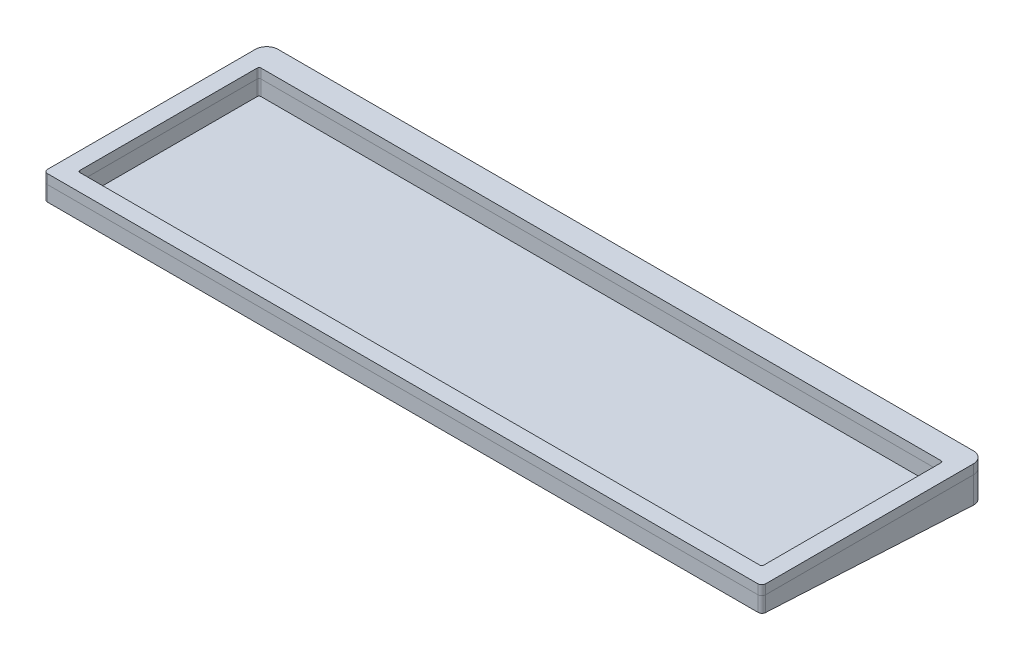
SolidWorks part; units mm, degrees
ref_plane "Front Plane" through (0, 0, 0) normal (0, 0, 1) x (1, 0, 0)
ref_plane "Top Plane" through (0, 0, 0) normal (0, 1, 0) x (1, 0, 0)
ref_plane "Right Plane" through (0, 0, 0) normal (1, 0, 0) x (0, 0, -1)
sketch "Sketch1" plane through (0, 0, 0) normal (0, 1, 0) x (1, 0, 0)
  line L1 (-178.825, 47.625) -> (178.825, 47.625)
  line L2 (-179.825, 46.625) -> (-179.825, -46.625)
  line L3 (-178.825, -47.625) -> (178.825, -47.625)
  line L4 (179.825, 46.625) -> (179.825, -46.625)
  line L5 (-179.825, 47.625) -> (179.825, -47.625) construction
  line L6 (-179.825, -47.625) -> (179.825, 47.625) construction
  arc A0 (178.825, -47.625) -> (179.825, -46.625) centre (178.825, -46.625) ccw
  arc A1 (178.825, 47.625) -> (179.825, 46.625) centre (178.825, 46.625) cw
  arc A2 (-179.825, -46.625) -> (-178.825, -47.625) centre (-178.825, -46.625) ccw
  arc A3 (-178.825, 47.625) -> (-179.825, 46.625) centre (-178.825, 46.625) ccw
  circle A4 centre (157.075, 19.175) radius 1.1
  circle A5 centre (136.925, -16.775) radius 1.1
  circle A6 centre (-153.475, 33.725) radius 1.1
  circle A7 centre (17.925, 22.275) radius 1.1
  circle A8 centre (17.875, -35.075) radius 1.1
  circle A9 centre (-130.375, -35.725) radius 1.1
  point P0 (0, 0)
  dimension "D3" = 1
  dimension "D4" = 2.2
  dimension "D7" = 2.2
  dimension "D8" = 2.2
  dimension "D9" = 2.2
  dimension "D10" = 2.2
  dimension "D11" = 2.2
  dimension "D1" = 359.65
  dimension "D2" = 95.25
  dimension "D5" = 22.75
  dimension "D6" = 28.45
  dimension "D12" = 42.9
  dimension "D13" = 30.85
  dimension "D14" = 25.35
  dimension "D15" = 161.9
  dimension "D16" = 12.55
  dimension "D17" = 161.95
  dimension "D18" = 11.9
  dimension "D19" = 49.45
  dimension "D20" = 13.9
  dimension "D21" = 26.35
sketch "Sketch2" plane through (0, 0, 0) normal (0, 1, 0) x (1, 0, 0)
  line L0 (-179.825, 46.625) -> (-179.825, -46.625) construction
  line L1 (-178.825, -47.625) -> (178.825, -47.625) construction
  line L2 (179.825, 46.625) -> (179.825, -46.625) construction
  line L3 (-178.825, 47.625) -> (178.825, 47.625) construction
  line L4 (-179.825, 46.625) -> (-179.825, -46.625)
  line L5 (-178.825, -47.625) -> (178.825, -47.625)
  line L6 (179.825, 46.625) -> (179.825, -46.625)
  line L7 (-178.825, 47.625) -> (178.825, 47.625)
  line L9 (-182.825, 60.625) -> (182.825, 60.625)
  line L10 (-188.825, 54.625) -> (-188.825, -54.625)
  line L11 (-186.825, -56.625) -> (186.825, -56.625)
  line L12 (188.825, 54.625) -> (188.825, -54.625)
  circle A0 centre (157.075, 19.175) radius 1.1 construction
  circle A1 centre (136.925, -16.775) radius 1.1 construction
  circle A2 centre (17.875, -35.075) radius 1.1 construction
  circle A3 centre (17.925, 22.275) radius 1.1 construction
  circle A4 centre (-153.475, 33.725) radius 1.1 construction
  circle A5 centre (-130.375, -35.725) radius 1.1 construction
  arc A6 (-179.825, -46.625) -> (-178.825, -47.625) centre (-178.825, -46.625) ccw construction
  arc A7 (178.825, -47.625) -> (179.825, -46.625) centre (178.825, -46.625) ccw construction
  arc A8 (179.825, 46.625) -> (178.825, 47.625) centre (178.825, 46.625) ccw construction
  arc A9 (-178.825, 47.625) -> (-179.825, 46.625) centre (-178.825, 46.625) ccw construction
  circle A10 centre (157.075, 19.175) radius 1.1
  circle A11 centre (136.925, -16.775) radius 1.1
  circle A12 centre (17.875, -35.075) radius 1.1
  circle A13 centre (17.925, 22.275) radius 1.1
  circle A14 centre (-153.475, 33.725) radius 1.1
  circle A15 centre (-130.375, -35.725) radius 1.1
  arc A16 (-179.825, -46.625) -> (-178.825, -47.625) centre (-178.825, -46.625) ccw
  arc A17 (178.825, -47.625) -> (179.825, -46.625) centre (178.825, -46.625) ccw
  arc A18 (179.825, 46.625) -> (178.825, 47.625) centre (178.825, 46.625) ccw
  arc A19 (-178.825, 47.625) -> (-179.825, 46.625) centre (-178.825, 46.625) ccw
  arc A20 (182.825, 60.625) -> (188.825, 54.625) centre (182.825, 54.625) cw
  arc A21 (-182.825, 60.625) -> (-188.825, 54.625) centre (-182.825, 54.625) ccw
  arc A22 (186.825, -56.625) -> (188.825, -54.625) centre (186.825, -54.625) ccw
  arc A23 (-188.825, -54.625) -> (-186.825, -56.625) centre (-186.825, -54.625) ccw
  point P30 (0, 0)
  dimension "D5" = 6
  dimension "D6" = 2
  dimension "D1" = 13
  dimension "D2" = 9
  dimension "D3" = 9
  dimension "D4" = 9
extrude "Boss-Extrude1" add sketch "Sketch2" along normal blind 13 contours L10 A23 L11 A22 L12 A20 L9 A21 A19 L7 A18 L6 A17 L5 A16 L4 region at (0, 0, -56.6707)
sketch "Sketch4" plane through (0, 0, 0) normal (0, -1, 0) x (1, 0, 0)
  line L0 (188.825, -54.625) -> (188.825, 54.625) construction
  line L1 (-182.825, -60.625) -> (182.825, -60.625) construction
  line L2 (-188.825, -54.625) -> (-188.825, 54.625) construction
  line L3 (-186.825, 56.625) -> (186.825, 56.625) construction
  line L4 (-179.825, 46.625) -> (-179.825, -46.625)
  line L5 (178.825, 47.625) -> (-178.825, 47.625)
  line L6 (179.825, -46.625) -> (179.825, 46.625)
  line L7 (-178.825, -47.625) -> (178.825, -47.625)
  line L8 (-179.825, 46.625) -> (-179.825, -46.625)
  line L10 (179.825, -46.625) -> (179.825, 46.625)
  line L11 (-178.825, -47.625) -> (178.825, -47.625)
  line L12 (188.825, -54.625) -> (188.825, 54.625)
  line L13 (-182.825, -60.625) -> (182.825, -60.625)
  line L14 (-188.825, -54.625) -> (-188.825, 54.625)
  line L15 (-186.825, 56.625) -> (186.825, 56.625)
  arc A0 (188.825, 54.625) -> (186.825, 56.625) centre (186.825, 54.625) ccw construction
  arc A1 (182.825, -60.625) -> (188.825, -54.625) centre (182.825, -54.625) ccw construction
  arc A2 (-188.825, -54.625) -> (-182.825, -60.625) centre (-182.825, -54.625) ccw construction
  arc A3 (-186.825, 56.625) -> (-188.825, 54.625) centre (-186.825, 54.625) ccw construction
  arc A4 (-179.825, -46.625) -> (-178.825, -47.625) centre (-178.825, -46.625) ccw
  arc A5 (-178.825, 47.625) -> (-179.825, 46.625) centre (-178.825, 46.625) ccw
  arc A6 (179.825, 46.625) -> (178.825, 47.625) centre (178.825, 46.625) ccw
  arc A7 (178.825, -47.625) -> (179.825, -46.625) centre (178.825, -46.625) ccw
  arc A8 (-179.825, -46.625) -> (-178.825, -47.625) centre (-178.825, -46.625) ccw
  arc A9 (-178.825, 47.625) -> (-179.825, 46.625) centre (-178.825, 46.625) ccw
  arc A10 (179.825, 46.625) -> (178.825, 47.625) centre (178.825, 46.625) ccw
  arc A11 (178.825, -47.625) -> (179.825, -46.625) centre (178.825, -46.625) ccw
  arc A12 (188.825, 54.625) -> (186.825, 56.625) centre (186.825, 54.625) ccw
  arc A13 (182.825, -60.625) -> (188.825, -54.625) centre (182.825, -54.625) ccw
  arc A14 (-188.825, -54.625) -> (-182.825, -60.625) centre (-182.825, -54.625) ccw
  arc A15 (-186.825, 56.625) -> (-188.825, 54.625) centre (-186.825, 54.625) ccw
  arc M9 (-178.825, -47.625) -> (-179.825, -46.625) centre (-178.825, -46.625) cw
  line M10 (-179.825, -46.625) -> (-179.825, 46.625)
  arc M11 (-179.825, 46.625) -> (-178.825, 47.625) centre (-178.825, 46.625) cw
  line M12 (-178.825, 47.625) -> (178.825, 47.625)
  arc M13 (178.825, 47.625) -> (179.825, 46.625) centre (178.825, 46.625) cw
  line M14 (179.825, 46.625) -> (179.825, -46.625)
  arc M15 (179.825, -46.625) -> (178.825, -47.625) centre (178.825, -46.625) cw
  line M16 (178.825, -47.625) -> (-178.825, -47.625)
  line M17 (-188.825, 54.625) -> (-188.825, -54.625)
  arc M18 (-188.825, -54.625) -> (-182.825, -60.625) centre (-182.825, -54.625) ccw
  line M19 (-182.825, -60.625) -> (182.825, -60.625)
  arc M20 (182.825, -60.625) -> (188.825, -54.625) centre (182.825, -54.625) ccw
  line M21 (188.825, -54.625) -> (188.825, 54.625)
  arc M22 (188.825, 54.625) -> (186.825, 56.625) centre (186.825, 54.625) ccw
  line M23 (186.825, 56.625) -> (-186.825, 56.625)
  arc M24 (-186.825, 56.625) -> (-188.825, 54.625) centre (-186.825, 54.625) ccw
  dimension "D1" = 0
extrude "Boss-Extrude3" add sketch "Sketch4" along normal blind 10.5 contours M24 M17 M18 M19 M20 M21 M22 M23 M16 M9 M10 M11 M12 M13 M14 M15 | M9 M16 M15 M14 M13 M12 M11 M10 region at (0, 0, 0) region at (184.2715, 0, -56.0715)
sketch "Sketch8" plane through (-188.825, 0, 0) normal (-1, 0, 0) x (0, 0, 1)
  line L0 (54.625, 0) -> (-57.625, 0) construction
  line L2 (-60.625, 13) -> (-60.625, -10.5) construction
  line L4 (-60.625, -6.1448) -> (-60.625, -10.5)
  line L5 (-60.625, -10.5) -> (56.625, -10.5)
  line L11 (56.625, 0) -> (56.625, -10.5)
  line L12 (56.625, 13) -> (56.625, -10.5) construction
  line L13 (-60.625, -6.1448) -> (56.625, 0)
  dimension "D1" = 2
  dimension "D2" = 10.5
  dimension "D3" = 87
extrude "Cut-Extrude4" cut sketch "Sketch8" against normal blind 400
sketch "Sketch9" plane through (0, 0, 0) normal (0, 1, 0) x (1, 0, 0)
  line L0 (-121.9453, 45.1) -> (-108.9453, 45.1)
  line L1 (-121.9453, 31.1) -> (-108.9453, 31.1)
  line L2 (-122.4453, 44.6) -> (-122.4453, 31.6)
  line L3 (-108.4453, 44.6) -> (-108.4453, 31.6)
  line L4 (-102.8953, 45.1) -> (-89.8953, 45.1)
  line L5 (-102.8953, 31.1) -> (-89.8953, 31.1)
  line L6 (-103.3953, 44.6) -> (-103.3953, 31.6)
  line L7 (-89.3953, 44.6) -> (-89.3953, 31.6)
  line L8 (-83.8453, 45.1) -> (-70.8453, 45.1)
  line L9 (-83.8453, 31.1) -> (-70.8453, 31.1)
  line L10 (-84.3453, 44.6) -> (-84.3453, 31.6)
  line L11 (-70.3453, 44.6) -> (-70.3453, 31.6)
  line L12 (-64.7953, 45.1) -> (-51.7953, 45.1)
  line L13 (-64.7953, 31.1) -> (-51.7953, 31.1)
  line L14 (-65.2953, 44.6) -> (-65.2953, 31.6)
  line L15 (-51.2953, 44.6) -> (-51.2953, 31.6)
  line L16 (-45.7453, 45.1) -> (-32.7453, 45.1)
  line L17 (-45.7453, 31.1) -> (-32.7453, 31.1)
  line L18 (-46.2453, 44.6) -> (-46.2453, 31.6)
  line L19 (-32.2453, 44.6) -> (-32.2453, 31.6)
  line L20 (-26.6953, 45.1) -> (-13.6953, 45.1)
  line L21 (-26.6953, 31.1) -> (-13.6953, 31.1)
  line L22 (-27.1953, 44.6) -> (-27.1953, 31.6)
  line L23 (-13.1953, 44.6) -> (-13.1953, 31.6)
  line L24 (-7.6453, 45.1) -> (5.3547, 45.1)
  line L25 (-7.6453, 31.1) -> (5.3547, 31.1)
  line L26 (-8.1453, 44.6) -> (-8.1453, 31.6)
  line L27 (5.8547, 44.6) -> (5.8547, 31.6)
  line L28 (11.4047, 45.1) -> (24.4047, 45.1)
  line L29 (11.4047, 31.1) -> (24.4047, 31.1)
  line L30 (10.9047, 44.6) -> (10.9047, 31.6)
  line L31 (24.9047, 44.6) -> (24.9047, 31.6)
  line L32 (30.4547, 45.1) -> (43.4547, 45.1)
  line L33 (30.4547, 31.1) -> (43.4547, 31.1)
  line L34 (29.9547, 44.6) -> (29.9547, 31.6)
  line L35 (43.9547, 44.6) -> (43.9547, 31.6)
  line L36 (49.5047, 45.1) -> (62.5047, 45.1)
  line L37 (49.5047, 31.1) -> (62.5047, 31.1)
  line L38 (49.0047, 44.6) -> (49.0047, 31.6)
  line L39 (63.0047, 44.6) -> (63.0047, 31.6)
  line L40 (68.5547, 45.1) -> (81.5547, 45.1)
  line L41 (68.5547, 31.1) -> (81.5547, 31.1)
  line L42 (68.0547, 44.6) -> (68.0547, 31.6)
  line L43 (82.0547, 44.6) -> (82.0547, 31.6)
  line L44 (87.6047, 45.1) -> (100.6047, 45.1)
  line L45 (87.6047, 31.1) -> (100.6047, 31.1)
  line L46 (87.1047, 44.6) -> (87.1047, 31.6)
  line L47 (101.1047, 44.6) -> (101.1047, 31.6)
  line L48 (106.6547, 45.1) -> (119.6547, 45.1)
  line L49 (106.6547, 31.1) -> (119.6547, 31.1)
  line L50 (106.1547, 44.6) -> (106.1547, 31.6)
  line L51 (120.1547, 44.6) -> (120.1547, 31.6)
  line L52 (135.2297, 45.1) -> (148.2297, 45.1)
  line L53 (135.2297, 31.1) -> (148.2297, 31.1)
  line L54 (134.7297, 44.6) -> (134.7297, 31.6)
  line L55 (148.7297, 44.6) -> (148.7297, 31.6)
  line L56 (150.6677, 44.1) -> (156.6677, 44.1)
  line L57 (150.6677, 29.1) -> (156.6677, 29.1)
  line L58 (150.1677, 43.6) -> (150.1677, 29.6)
  line L59 (157.1677, 43.6) -> (157.1677, 29.6)
  line L60 (126.7917, 44.1) -> (132.7917, 44.1)
  line L61 (126.7917, 29.1) -> (132.7917, 29.1)
  line L62 (126.2917, 43.6) -> (126.2917, 29.6)
  line L63 (133.2917, 43.6) -> (133.2917, 29.6)
  line L64 (163.8047, 45.1) -> (176.8047, 45.1)
  line L65 (163.8047, 31.1) -> (176.8047, 31.1)
  line L66 (163.3047, 44.6) -> (163.3047, 31.6)
  line L67 (177.3047, 44.6) -> (177.3047, 31.6)
  line L68 (-117.1828, 26.05) -> (-104.1828, 26.05)
  line L69 (-117.1828, 12.05) -> (-104.1828, 12.05)
  line L70 (-117.6828, 25.55) -> (-117.6828, 12.55)
  line L71 (-103.6828, 25.55) -> (-103.6828, 12.55)
  line L72 (-93.3703, 26.05) -> (-80.3703, 26.05)
  line L73 (-93.3703, 12.05) -> (-80.3703, 12.05)
  line L74 (-93.8703, 25.55) -> (-93.8703, 12.55)
  line L75 (-79.8703, 25.55) -> (-79.8703, 12.55)
  line L76 (-74.3203, 26.05) -> (-61.3203, 26.05)
  line L77 (-74.3203, 12.05) -> (-61.3203, 12.05)
  line L78 (-74.8203, 25.55) -> (-74.8203, 12.55)
  line L79 (-60.8203, 25.55) -> (-60.8203, 12.55)
  line L80 (-55.2703, 26.05) -> (-42.2703, 26.05)
  line L81 (-55.2703, 12.05) -> (-42.2703, 12.05)
  line L82 (-55.7703, 25.55) -> (-55.7703, 12.55)
  line L83 (-41.7703, 25.55) -> (-41.7703, 12.55)
  line L84 (-36.2203, 26.05) -> (-23.2203, 26.05)
  line L85 (-36.2203, 12.05) -> (-23.2203, 12.05)
  line L86 (-36.7203, 25.55) -> (-36.7203, 12.55)
  line L87 (-22.7203, 25.55) -> (-22.7203, 12.55)
  line L88 (-17.1703, 26.05) -> (-4.1703, 26.05)
  line L89 (-17.1703, 12.05) -> (-4.1703, 12.05)
  line L90 (-17.6703, 25.55) -> (-17.6703, 12.55)
  line L91 (-3.6703, 25.55) -> (-3.6703, 12.55)
  line L92 (1.8797, 26.05) -> (14.8797, 26.05)
  line L93 (1.8797, 12.05) -> (14.8797, 12.05)
  line L94 (1.3797, 25.55) -> (1.3797, 12.55)
  line L95 (15.3797, 25.55) -> (15.3797, 12.55)
  line L96 (20.9297, 26.05) -> (33.9297, 26.05)
  line L97 (20.9297, 12.05) -> (33.9297, 12.05)
  line L98 (20.4297, 25.55) -> (20.4297, 12.55)
  line L99 (34.4297, 25.55) -> (34.4297, 12.55)
  line L100 (39.9797, 26.05) -> (52.9797, 26.05)
  line L101 (39.9797, 12.05) -> (52.9797, 12.05)
  line L102 (39.4797, 25.55) -> (39.4797, 12.55)
  line L103 (53.4797, 25.55) -> (53.4797, 12.55)
  line L104 (59.0297, 26.05) -> (72.0297, 26.05)
  line L105 (59.0297, 12.05) -> (72.0297, 12.05)
  line L106 (58.5297, 25.55) -> (58.5297, 12.55)
  line L107 (72.5297, 25.55) -> (72.5297, 12.55)
  line L108 (78.0797, 26.05) -> (91.0797, 26.05)
  line L109 (78.0797, 12.05) -> (91.0797, 12.05)
  line L110 (77.5797, 25.55) -> (77.5797, 12.55)
  line L111 (91.5797, 25.55) -> (91.5797, 12.55)
  line L112 (97.1297, 26.05) -> (110.1297, 26.05)
  line L113 (97.1297, 12.05) -> (110.1297, 12.05)
  line L114 (96.6297, 25.55) -> (96.6297, 12.55)
  line L115 (110.6297, 25.55) -> (110.6297, 12.55)
  line L116 (116.1797, 26.05) -> (129.1797, 26.05)
  line L117 (116.1797, 12.05) -> (129.1797, 12.05)
  line L118 (115.6797, 25.55) -> (115.6797, 12.55)
  line L119 (129.6797, 25.55) -> (129.6797, 12.55)
  line L120 (139.9922, 26.05) -> (152.9922, 26.05)
  line L121 (139.9922, 12.05) -> (152.9922, 12.05)
  line L122 (139.4922, 25.55) -> (139.4922, 12.55)
  line L123 (153.4922, 25.55) -> (153.4922, 12.55)
  line L124 (163.8047, 26.05) -> (176.8047, 26.05)
  line L125 (163.8047, 12.05) -> (176.8047, 12.05)
  line L126 (163.3047, 25.55) -> (163.3047, 12.55)
  line L127 (177.3047, 25.55) -> (177.3047, 12.55)
  line L128 (-114.8016, 7) -> (-101.8016, 7)
  line L129 (-114.8016, -7) -> (-101.8016, -7)
  line L130 (-115.3016, 6.5) -> (-115.3016, -6.5)
  line L131 (-101.3016, 6.5) -> (-101.3016, -6.5)
  line L132 (-88.6078, 7) -> (-75.6078, 7)
  line L133 (-88.6078, -7) -> (-75.6078, -7)
  line L134 (-89.1078, 6.5) -> (-89.1078, -6.5)
  line L135 (-75.1078, 6.5) -> (-75.1078, -6.5)
  line L136 (-69.5578, 7) -> (-56.5578, 7)
  line L137 (-69.5578, -7) -> (-56.5578, -7)
  line L138 (-70.0578, 6.5) -> (-70.0578, -6.5)
  line L139 (-56.0578, 6.5) -> (-56.0578, -6.5)
  line L140 (-50.5078, 7) -> (-37.5078, 7)
  line L141 (-50.5078, -7) -> (-37.5078, -7)
  line L142 (-51.0078, 6.5) -> (-51.0078, -6.5)
  line L143 (-37.0078, 6.5) -> (-37.0078, -6.5)
  line L144 (-31.4578, 7) -> (-18.4578, 7)
  line L145 (-31.4578, -7) -> (-18.4578, -7)
  line L146 (-31.9578, 6.5) -> (-31.9578, -6.5)
  line L147 (-17.9578, 6.5) -> (-17.9578, -6.5)
  line L148 (-12.4078, 7) -> (0.5922, 7)
  line L149 (-12.4078, -7) -> (0.5922, -7)
  line L150 (-12.9078, 6.5) -> (-12.9078, -6.5)
  line L151 (1.0922, 6.5) -> (1.0922, -6.5)
  line L152 (6.6422, 7) -> (19.6422, 7)
  line L153 (6.6422, -7) -> (19.6422, -7)
  line L154 (6.1422, 6.5) -> (6.1422, -6.5)
  line L155 (20.1422, 6.5) -> (20.1422, -6.5)
  line L156 (25.6922, 7) -> (38.6922, 7)
  line L157 (25.6922, -7) -> (38.6922, -7)
  line L158 (25.1922, 6.5) -> (25.1922, -6.5)
  line L159 (39.1922, 6.5) -> (39.1922, -6.5)
  line L160 (44.7422, 7) -> (57.7422, 7)
  line L161 (44.7422, -7) -> (57.7422, -7)
  line L162 (44.2422, 6.5) -> (44.2422, -6.5)
  line L163 (58.2422, 6.5) -> (58.2422, -6.5)
  line L164 (63.7922, 7) -> (76.7922, 7)
  line L165 (63.7922, -7) -> (76.7922, -7)
  line L166 (63.2922, 6.5) -> (63.2922, -6.5)
  line L167 (77.2922, 6.5) -> (77.2922, -6.5)
  line L168 (82.8422, 7) -> (95.8422, 7)
  line L169 (82.8422, -7) -> (95.8422, -7)
  line L170 (82.3422, 6.5) -> (82.3422, -6.5)
  line L171 (96.3422, 6.5) -> (96.3422, -6.5)
  line L172 (101.8922, 7) -> (114.8922, 7)
  line L173 (101.8922, -7) -> (114.8922, -7)
  line L174 (101.3922, 6.5) -> (101.3922, -6.5)
  line L175 (115.3922, 6.5) -> (115.3922, -6.5)
  line L176 (132.8484, 7) -> (145.8484, 7)
  line L177 (132.8484, -7) -> (145.8484, -7)
  line L178 (132.3484, 6.5) -> (132.3484, -6.5)
  line L179 (146.3484, 6.5) -> (146.3484, -6.5)
  line L180 (148.2864, 6) -> (154.2864, 6)
  line L181 (148.2864, -9) -> (154.2864, -9)
  line L182 (147.7864, 5.5) -> (147.7864, -8.5)
  line L183 (154.7864, 5.5) -> (154.7864, -8.5)
  line L184 (124.4104, 6) -> (130.4104, 6)
  line L185 (124.4104, -9) -> (130.4104, -9)
  line L186 (123.9104, 5.5) -> (123.9104, -8.5)
  line L187 (130.9104, 5.5) -> (130.9104, -8.5)
  line L188 (163.8047, 7) -> (176.8047, 7)
  line L189 (163.8047, -7) -> (176.8047, -7)
  line L190 (163.3047, 6.5) -> (163.3047, -6.5)
  line L191 (177.3047, 6.5) -> (177.3047, -6.5)
  line L192 (-110.0391, -12.05) -> (-97.0391, -12.05)
  line L193 (-110.0391, -26.05) -> (-97.0391, -26.05)
  line L194 (-110.5391, -12.55) -> (-110.5391, -25.55)
  line L195 (-96.5391, -12.55) -> (-96.5391, -25.55)
  line L196 (-94.6011, -13.05) -> (-88.6011, -13.05)
  line L197 (-94.6011, -28.05) -> (-88.6011, -28.05)
  line L198 (-95.1011, -13.55) -> (-95.1011, -27.55)
  line L199 (-88.1011, -13.55) -> (-88.1011, -27.55)
  line L200 (-118.4771, -13.05) -> (-112.4771, -13.05)
  line L201 (-118.4771, -28.05) -> (-112.4771, -28.05)
  line L202 (-118.9771, -13.55) -> (-118.9771, -27.55)
  line L203 (-111.9771, -13.55) -> (-111.9771, -27.55)
  line L204 (-79.0828, -12.05) -> (-66.0828, -12.05)
  line L205 (-79.0828, -26.05) -> (-66.0828, -26.05)
  line L206 (-79.5828, -12.55) -> (-79.5828, -25.55)
  line L207 (-65.5828, -12.55) -> (-65.5828, -25.55)
  line L208 (-60.0328, -12.05) -> (-47.0328, -12.05)
  line L209 (-60.0328, -26.05) -> (-47.0328, -26.05)
  line L210 (-60.5328, -12.55) -> (-60.5328, -25.55)
  line L211 (-46.5328, -12.55) -> (-46.5328, -25.55)
  line L212 (-40.9828, -12.05) -> (-27.9828, -12.05)
  line L213 (-40.9828, -26.05) -> (-27.9828, -26.05)
  line L214 (-41.4828, -12.55) -> (-41.4828, -25.55)
  line L215 (-27.4828, -12.55) -> (-27.4828, -25.55)
  line L216 (-21.9328, -12.05) -> (-8.9328, -12.05)
  line L217 (-21.9328, -26.05) -> (-8.9328, -26.05)
  line L218 (-22.4328, -12.55) -> (-22.4328, -25.55)
  line L219 (-8.4328, -12.55) -> (-8.4328, -25.55)
  line L220 (-2.8828, -12.05) -> (10.1172, -12.05)
  line L221 (-2.8828, -26.05) -> (10.1172, -26.05)
  line L222 (-3.3828, -12.55) -> (-3.3828, -25.55)
  line L223 (10.6172, -12.55) -> (10.6172, -25.55)
  line L224 (16.1672, -12.05) -> (29.1672, -12.05)
  line L225 (16.1672, -26.05) -> (29.1672, -26.05)
  line L226 (15.6672, -12.55) -> (15.6672, -25.55)
  line L227 (29.6672, -12.55) -> (29.6672, -25.55)
  line L228 (35.2172, -12.05) -> (48.2172, -12.05)
  line L229 (35.2172, -26.05) -> (48.2172, -26.05)
  line L230 (34.7172, -12.55) -> (34.7172, -25.55)
  line L231 (48.7172, -12.55) -> (48.7172, -25.55)
  line L232 (54.2672, -12.05) -> (67.2672, -12.05)
  line L233 (54.2672, -26.05) -> (67.2672, -26.05)
  line L234 (53.7672, -12.55) -> (53.7672, -25.55)
  line L235 (67.7672, -12.55) -> (67.7672, -25.55)
  line L236 (73.3172, -12.05) -> (86.3172, -12.05)
  line L237 (73.3172, -26.05) -> (86.3172, -26.05)
  line L238 (72.8172, -12.55) -> (72.8172, -25.55)
  line L239 (86.8172, -12.55) -> (86.8172, -25.55)
  line L240 (92.3672, -12.05) -> (105.3672, -12.05)
  line L241 (92.3672, -26.05) -> (105.3672, -26.05)
  line L242 (91.8672, -12.55) -> (91.8672, -25.55)
  line L243 (105.8672, -12.55) -> (105.8672, -25.55)
  line L244 (118.5609, -12.05) -> (131.5609, -12.05)
  line L245 (118.5609, -26.05) -> (131.5609, -26.05)
  line L246 (118.0609, -12.55) -> (118.0609, -25.55)
  line L247 (132.0609, -12.55) -> (132.0609, -25.55)
  line L248 (144.7547, -12.05) -> (157.7547, -12.05)
  line L249 (144.7547, -26.05) -> (157.7547, -26.05)
  line L250 (144.2547, -12.55) -> (144.2547, -25.55)
  line L251 (158.2547, -12.55) -> (158.2547, -25.55)
  line L252 (163.8047, -12.05) -> (176.8047, -12.05)
  line L253 (163.8047, -26.05) -> (176.8047, -26.05)
  line L254 (163.3047, -12.55) -> (163.3047, -25.55)
  line L255 (177.3047, -12.55) -> (177.3047, -25.55)
  line L256 (-119.5641, -31.1) -> (-106.5641, -31.1)
  line L257 (-119.5641, -45.1) -> (-106.5641, -45.1)
  line L258 (-120.0641, -31.6) -> (-120.0641, -44.6)
  line L259 (-106.0641, -31.6) -> (-106.0641, -44.6)
  line L260 (-95.7516, -31.1) -> (-82.7516, -31.1)
  line L261 (-95.7516, -45.1) -> (-82.7516, -45.1)
  line L262 (-96.2516, -31.6) -> (-96.2516, -44.6)
  line L263 (-82.2516, -31.6) -> (-82.2516, -44.6)
  line L264 (-71.9391, -31.1) -> (-58.9391, -31.1)
  line L265 (-71.9391, -45.1) -> (-58.9391, -45.1)
  line L266 (-72.4391, -31.6) -> (-72.4391, -44.6)
  line L267 (-58.4391, -31.6) -> (-58.4391, -44.6)
  line L268 (-0.5016, -31.1) -> (12.4984, -31.1)
  line L269 (-0.5016, -45.1) -> (12.4984, -45.1)
  line L270 (-1.0016, -31.6) -> (-1.0016, -44.6)
  line L271 (12.9984, -31.6) -> (12.9984, -44.6)
  line L272 (52.9984, -32.1) -> (58.9984, -32.1)
  line L273 (52.9984, -47.1) -> (58.9984, -47.1)
  line L274 (52.4984, -32.6) -> (52.4984, -46.6)
  line L275 (59.4984, -32.6) -> (59.4984, -46.6)
  line L276 (-47.0016, -32.1) -> (-41.0016, -32.1)
  line L277 (-47.0016, -47.1) -> (-41.0016, -47.1)
  line L278 (-47.5016, -32.6) -> (-47.5016, -46.6)
  line L279 (-40.5016, -32.6) -> (-40.5016, -46.6)
  line L280 (68.5547, -31.1) -> (81.5547, -31.1)
  line L281 (68.5547, -45.1) -> (81.5547, -45.1)
  line L282 (68.0547, -31.6) -> (68.0547, -44.6)
  line L283 (82.0547, -31.6) -> (82.0547, -44.6)
  line L284 (87.6047, -31.1) -> (100.6047, -31.1)
  line L285 (87.6047, -45.1) -> (100.6047, -45.1)
  line L286 (87.1047, -31.6) -> (87.1047, -44.6)
  line L287 (101.1047, -31.6) -> (101.1047, -44.6)
  line L288 (106.6547, -31.1) -> (119.6547, -31.1)
  line L289 (106.6547, -45.1) -> (119.6547, -45.1)
  line L290 (106.1547, -31.6) -> (106.1547, -44.6)
  line L291 (120.1547, -31.6) -> (120.1547, -44.6)
  line L292 (125.7047, -31.1) -> (138.7047, -31.1)
  line L293 (125.7047, -45.1) -> (138.7047, -45.1)
  line L294 (125.2047, -31.6) -> (125.2047, -44.6)
  line L295 (139.2047, -31.6) -> (139.2047, -44.6)
  line L296 (144.7547, -31.1) -> (157.7547, -31.1)
  line L297 (144.7547, -45.1) -> (157.7547, -45.1)
  line L298 (144.2547, -31.6) -> (144.2547, -44.6)
  line L299 (158.2547, -31.6) -> (158.2547, -44.6)
  line L300 (163.8047, -31.1) -> (176.8047, -31.1)
  line L301 (163.8047, -45.1) -> (176.8047, -45.1)
  line L302 (163.3047, -31.6) -> (163.3047, -44.6)
  line L303 (177.3047, -31.6) -> (177.3047, -44.6)
  line L304 (-124.9703, 47.625) -> (-103.2456, 47.625)
  line L305 (-124.9703, -47.625) -> (179.8297, -47.625)
  line L306 (-124.9703, 47.625) -> (-124.9703, -47.625)
  line L307 (179.8297, 47.625) -> (179.8297, -47.625)
  line L308 (-103.2456, 53.125) -> (-103.2456, 47.625)
  line L309 (-124.9703, 47.625) -> (-103.2456, 47.625)
  line L311 (-101.2456, 55.125) -> (-90.2456, 55.125)
  line L312 (-88.2456, 47.625) -> (-88.2456, 53.125)
  line L313 (-23.2456, 53.125) -> (-23.2456, 47.625)
  line L314 (-21.2456, 55.125) -> (-10.2456, 55.125)
  line L315 (-8.2456, 47.625) -> (-8.2456, 53.125)
  line L316 (56.7544, 53.125) -> (56.7544, 47.625)
  line L317 (58.7544, 55.125) -> (69.7544, 55.125)
  line L318 (71.7544, 47.625) -> (71.7544, 53.125)
  line L319 (136.7544, 53.125) -> (136.7544, 47.625)
  line L320 (138.7544, 55.125) -> (149.7544, 55.125)
  line L321 (151.7544, 47.625) -> (151.7544, 53.125)
  line L322 (-88.2456, 47.625) -> (-23.2456, 47.625)
  line L323 (-8.2456, 47.625) -> (56.7544, 47.625)
  line L324 (71.7544, 47.625) -> (136.7544, 47.625)
  line L325 (151.7544, 47.625) -> (179.8297, 47.625)
  arc A0 (-121.9453, 45.1) -> (-122.4453, 44.6) centre (-121.9453, 44.6) ccw
  arc A1 (-108.4453, 44.6) -> (-108.9453, 45.1) centre (-108.9453, 44.6) ccw
  arc A2 (-122.4453, 31.6) -> (-121.9453, 31.1) centre (-121.9453, 31.6) ccw
  arc A3 (-108.9453, 31.1) -> (-108.4453, 31.6) centre (-108.9453, 31.6) ccw
  arc A4 (-102.8953, 45.1) -> (-103.3953, 44.6) centre (-102.8953, 44.6) ccw
  arc A5 (-89.3953, 44.6) -> (-89.8953, 45.1) centre (-89.8953, 44.6) ccw
  arc A6 (-103.3953, 31.6) -> (-102.8953, 31.1) centre (-102.8953, 31.6) ccw
  arc A7 (-89.8953, 31.1) -> (-89.3953, 31.6) centre (-89.8953, 31.6) ccw
  arc A8 (-83.8453, 45.1) -> (-84.3453, 44.6) centre (-83.8453, 44.6) ccw
  arc A9 (-70.3453, 44.6) -> (-70.8453, 45.1) centre (-70.8453, 44.6) ccw
  arc A10 (-84.3453, 31.6) -> (-83.8453, 31.1) centre (-83.8453, 31.6) ccw
  arc A11 (-70.8453, 31.1) -> (-70.3453, 31.6) centre (-70.8453, 31.6) ccw
  arc A12 (-64.7953, 45.1) -> (-65.2953, 44.6) centre (-64.7953, 44.6) ccw
  arc A13 (-51.2953, 44.6) -> (-51.7953, 45.1) centre (-51.7953, 44.6) ccw
  arc A14 (-65.2953, 31.6) -> (-64.7953, 31.1) centre (-64.7953, 31.6) ccw
  arc A15 (-51.7953, 31.1) -> (-51.2953, 31.6) centre (-51.7953, 31.6) ccw
  arc A16 (-45.7453, 45.1) -> (-46.2453, 44.6) centre (-45.7453, 44.6) ccw
  arc A17 (-32.2453, 44.6) -> (-32.7453, 45.1) centre (-32.7453, 44.6) ccw
  arc A18 (-46.2453, 31.6) -> (-45.7453, 31.1) centre (-45.7453, 31.6) ccw
  arc A19 (-32.7453, 31.1) -> (-32.2453, 31.6) centre (-32.7453, 31.6) ccw
  arc A20 (-26.6953, 45.1) -> (-27.1953, 44.6) centre (-26.6953, 44.6) ccw
  arc A21 (-13.1953, 44.6) -> (-13.6953, 45.1) centre (-13.6953, 44.6) ccw
  arc A22 (-27.1953, 31.6) -> (-26.6953, 31.1) centre (-26.6953, 31.6) ccw
  arc A23 (-13.6953, 31.1) -> (-13.1953, 31.6) centre (-13.6953, 31.6) ccw
  arc A24 (-7.6453, 45.1) -> (-8.1453, 44.6) centre (-7.6453, 44.6) ccw
  arc A25 (5.8547, 44.6) -> (5.3547, 45.1) centre (5.3547, 44.6) ccw
  arc A26 (-8.1453, 31.6) -> (-7.6453, 31.1) centre (-7.6453, 31.6) ccw
  arc A27 (5.3547, 31.1) -> (5.8547, 31.6) centre (5.3547, 31.6) ccw
  arc A28 (11.4047, 45.1) -> (10.9047, 44.6) centre (11.4047, 44.6) ccw
  arc A29 (24.9047, 44.6) -> (24.4047, 45.1) centre (24.4047, 44.6) ccw
  arc A30 (10.9047, 31.6) -> (11.4047, 31.1) centre (11.4047, 31.6) ccw
  arc A31 (24.4047, 31.1) -> (24.9047, 31.6) centre (24.4047, 31.6) ccw
  arc A32 (30.4547, 45.1) -> (29.9547, 44.6) centre (30.4547, 44.6) ccw
  arc A33 (43.9547, 44.6) -> (43.4547, 45.1) centre (43.4547, 44.6) ccw
  arc A34 (29.9547, 31.6) -> (30.4547, 31.1) centre (30.4547, 31.6) ccw
  arc A35 (43.4547, 31.1) -> (43.9547, 31.6) centre (43.4547, 31.6) ccw
  arc A36 (49.5047, 45.1) -> (49.0047, 44.6) centre (49.5047, 44.6) ccw
  arc A37 (63.0047, 44.6) -> (62.5047, 45.1) centre (62.5047, 44.6) ccw
  arc A38 (49.0047, 31.6) -> (49.5047, 31.1) centre (49.5047, 31.6) ccw
  arc A39 (62.5047, 31.1) -> (63.0047, 31.6) centre (62.5047, 31.6) ccw
  arc A40 (68.5547, 45.1) -> (68.0547, 44.6) centre (68.5547, 44.6) ccw
  arc A41 (82.0547, 44.6) -> (81.5547, 45.1) centre (81.5547, 44.6) ccw
  arc A42 (68.0547, 31.6) -> (68.5547, 31.1) centre (68.5547, 31.6) ccw
  arc A43 (81.5547, 31.1) -> (82.0547, 31.6) centre (81.5547, 31.6) ccw
  arc A44 (87.6047, 45.1) -> (87.1047, 44.6) centre (87.6047, 44.6) ccw
  arc A45 (101.1047, 44.6) -> (100.6047, 45.1) centre (100.6047, 44.6) ccw
  arc A46 (87.1047, 31.6) -> (87.6047, 31.1) centre (87.6047, 31.6) ccw
  arc A47 (100.6047, 31.1) -> (101.1047, 31.6) centre (100.6047, 31.6) ccw
  arc A48 (106.6547, 45.1) -> (106.1547, 44.6) centre (106.6547, 44.6) ccw
  arc A49 (120.1547, 44.6) -> (119.6547, 45.1) centre (119.6547, 44.6) ccw
  arc A50 (106.1547, 31.6) -> (106.6547, 31.1) centre (106.6547, 31.6) ccw
  arc A51 (119.6547, 31.1) -> (120.1547, 31.6) centre (119.6547, 31.6) ccw
  arc A52 (135.2297, 45.1) -> (134.7297, 44.6) centre (135.2297, 44.6) ccw
  arc A53 (148.7297, 44.6) -> (148.2297, 45.1) centre (148.2297, 44.6) ccw
  arc A54 (134.7297, 31.6) -> (135.2297, 31.1) centre (135.2297, 31.6) ccw
  arc A55 (148.2297, 31.1) -> (148.7297, 31.6) centre (148.2297, 31.6) ccw
  arc A56 (150.6677, 44.1) -> (150.1677, 43.6) centre (150.6677, 43.6) ccw
  arc A57 (157.1677, 43.6) -> (156.6677, 44.1) centre (156.6677, 43.6) ccw
  arc A58 (150.1677, 29.6) -> (150.6677, 29.1) centre (150.6677, 29.6) ccw
  arc A59 (156.6677, 29.1) -> (157.1677, 29.6) centre (156.6677, 29.6) ccw
  arc A60 (126.7917, 44.1) -> (126.2917, 43.6) centre (126.7917, 43.6) ccw
  arc A61 (133.2917, 43.6) -> (132.7917, 44.1) centre (132.7917, 43.6) ccw
  arc A62 (126.2917, 29.6) -> (126.7917, 29.1) centre (126.7917, 29.6) ccw
  arc A63 (132.7917, 29.1) -> (133.2917, 29.6) centre (132.7917, 29.6) ccw
  arc A64 (163.8047, 45.1) -> (163.3047, 44.6) centre (163.8047, 44.6) ccw
  arc A65 (177.3047, 44.6) -> (176.8047, 45.1) centre (176.8047, 44.6) ccw
  arc A66 (163.3047, 31.6) -> (163.8047, 31.1) centre (163.8047, 31.6) ccw
  arc A67 (176.8047, 31.1) -> (177.3047, 31.6) centre (176.8047, 31.6) ccw
  arc A68 (-117.1828, 26.05) -> (-117.6828, 25.55) centre (-117.1828, 25.55) ccw
  arc A69 (-103.6828, 25.55) -> (-104.1828, 26.05) centre (-104.1828, 25.55) ccw
  arc A70 (-117.6828, 12.55) -> (-117.1828, 12.05) centre (-117.1828, 12.55) ccw
  arc A71 (-104.1828, 12.05) -> (-103.6828, 12.55) centre (-104.1828, 12.55) ccw
  arc A72 (-93.3703, 26.05) -> (-93.8703, 25.55) centre (-93.3703, 25.55) ccw
  arc A73 (-79.8703, 25.55) -> (-80.3703, 26.05) centre (-80.3703, 25.55) ccw
  arc A74 (-93.8703, 12.55) -> (-93.3703, 12.05) centre (-93.3703, 12.55) ccw
  arc A75 (-80.3703, 12.05) -> (-79.8703, 12.55) centre (-80.3703, 12.55) ccw
  arc A76 (-74.3203, 26.05) -> (-74.8203, 25.55) centre (-74.3203, 25.55) ccw
  arc A77 (-60.8203, 25.55) -> (-61.3203, 26.05) centre (-61.3203, 25.55) ccw
  arc A78 (-74.8203, 12.55) -> (-74.3203, 12.05) centre (-74.3203, 12.55) ccw
  arc A79 (-61.3203, 12.05) -> (-60.8203, 12.55) centre (-61.3203, 12.55) ccw
  arc A80 (-55.2703, 26.05) -> (-55.7703, 25.55) centre (-55.2703, 25.55) ccw
  arc A81 (-41.7703, 25.55) -> (-42.2703, 26.05) centre (-42.2703, 25.55) ccw
  arc A82 (-55.7703, 12.55) -> (-55.2703, 12.05) centre (-55.2703, 12.55) ccw
  arc A83 (-42.2703, 12.05) -> (-41.7703, 12.55) centre (-42.2703, 12.55) ccw
  arc A84 (-36.2203, 26.05) -> (-36.7203, 25.55) centre (-36.2203, 25.55) ccw
  arc A85 (-22.7203, 25.55) -> (-23.2203, 26.05) centre (-23.2203, 25.55) ccw
  arc A86 (-36.7203, 12.55) -> (-36.2203, 12.05) centre (-36.2203, 12.55) ccw
  arc A87 (-23.2203, 12.05) -> (-22.7203, 12.55) centre (-23.2203, 12.55) ccw
  arc A88 (-17.1703, 26.05) -> (-17.6703, 25.55) centre (-17.1703, 25.55) ccw
  arc A89 (-3.6703, 25.55) -> (-4.1703, 26.05) centre (-4.1703, 25.55) ccw
  arc A90 (-17.6703, 12.55) -> (-17.1703, 12.05) centre (-17.1703, 12.55) ccw
  arc A91 (-4.1703, 12.05) -> (-3.6703, 12.55) centre (-4.1703, 12.55) ccw
  arc A92 (1.8797, 26.05) -> (1.3797, 25.55) centre (1.8797, 25.55) ccw
  arc A93 (15.3797, 25.55) -> (14.8797, 26.05) centre (14.8797, 25.55) ccw
  arc A94 (1.3797, 12.55) -> (1.8797, 12.05) centre (1.8797, 12.55) ccw
  arc A95 (14.8797, 12.05) -> (15.3797, 12.55) centre (14.8797, 12.55) ccw
  arc A96 (20.9297, 26.05) -> (20.4297, 25.55) centre (20.9297, 25.55) ccw
  arc A97 (34.4297, 25.55) -> (33.9297, 26.05) centre (33.9297, 25.55) ccw
  arc A98 (20.4297, 12.55) -> (20.9297, 12.05) centre (20.9297, 12.55) ccw
  arc A99 (33.9297, 12.05) -> (34.4297, 12.55) centre (33.9297, 12.55) ccw
  arc A100 (39.9797, 26.05) -> (39.4797, 25.55) centre (39.9797, 25.55) ccw
  arc A101 (53.4797, 25.55) -> (52.9797, 26.05) centre (52.9797, 25.55) ccw
  arc A102 (39.4797, 12.55) -> (39.9797, 12.05) centre (39.9797, 12.55) ccw
  arc A103 (52.9797, 12.05) -> (53.4797, 12.55) centre (52.9797, 12.55) ccw
  arc A104 (59.0297, 26.05) -> (58.5297, 25.55) centre (59.0297, 25.55) ccw
  arc A105 (72.5297, 25.55) -> (72.0297, 26.05) centre (72.0297, 25.55) ccw
  arc A106 (58.5297, 12.55) -> (59.0297, 12.05) centre (59.0297, 12.55) ccw
  arc A107 (72.0297, 12.05) -> (72.5297, 12.55) centre (72.0297, 12.55) ccw
  arc A108 (78.0797, 26.05) -> (77.5797, 25.55) centre (78.0797, 25.55) ccw
  arc A109 (91.5797, 25.55) -> (91.0797, 26.05) centre (91.0797, 25.55) ccw
  arc A110 (77.5797, 12.55) -> (78.0797, 12.05) centre (78.0797, 12.55) ccw
  arc A111 (91.0797, 12.05) -> (91.5797, 12.55) centre (91.0797, 12.55) ccw
  arc A112 (97.1297, 26.05) -> (96.6297, 25.55) centre (97.1297, 25.55) ccw
  arc A113 (110.6297, 25.55) -> (110.1297, 26.05) centre (110.1297, 25.55) ccw
  arc A114 (96.6297, 12.55) -> (97.1297, 12.05) centre (97.1297, 12.55) ccw
  arc A115 (110.1297, 12.05) -> (110.6297, 12.55) centre (110.1297, 12.55) ccw
  arc A116 (116.1797, 26.05) -> (115.6797, 25.55) centre (116.1797, 25.55) ccw
  arc A117 (129.6797, 25.55) -> (129.1797, 26.05) centre (129.1797, 25.55) ccw
  arc A118 (115.6797, 12.55) -> (116.1797, 12.05) centre (116.1797, 12.55) ccw
  arc A119 (129.1797, 12.05) -> (129.6797, 12.55) centre (129.1797, 12.55) ccw
  arc A120 (139.9922, 26.05) -> (139.4922, 25.55) centre (139.9922, 25.55) ccw
  arc A121 (153.4922, 25.55) -> (152.9922, 26.05) centre (152.9922, 25.55) ccw
  arc A122 (139.4922, 12.55) -> (139.9922, 12.05) centre (139.9922, 12.55) ccw
  arc A123 (152.9922, 12.05) -> (153.4922, 12.55) centre (152.9922, 12.55) ccw
  arc A124 (163.8047, 26.05) -> (163.3047, 25.55) centre (163.8047, 25.55) ccw
  arc A125 (177.3047, 25.55) -> (176.8047, 26.05) centre (176.8047, 25.55) ccw
  arc A126 (163.3047, 12.55) -> (163.8047, 12.05) centre (163.8047, 12.55) ccw
  arc A127 (176.8047, 12.05) -> (177.3047, 12.55) centre (176.8047, 12.55) ccw
  arc A128 (-114.8016, 7) -> (-115.3016, 6.5) centre (-114.8016, 6.5) ccw
  arc A129 (-101.3016, 6.5) -> (-101.8016, 7) centre (-101.8016, 6.5) ccw
  arc A130 (-115.3016, -6.5) -> (-114.8016, -7) centre (-114.8016, -6.5) ccw
  arc A131 (-101.8016, -7) -> (-101.3016, -6.5) centre (-101.8016, -6.5) ccw
  arc A132 (-88.6078, 7) -> (-89.1078, 6.5) centre (-88.6078, 6.5) ccw
  arc A133 (-75.1078, 6.5) -> (-75.6078, 7) centre (-75.6078, 6.5) ccw
  arc A134 (-89.1078, -6.5) -> (-88.6078, -7) centre (-88.6078, -6.5) ccw
  arc A135 (-75.6078, -7) -> (-75.1078, -6.5) centre (-75.6078, -6.5) ccw
  arc A136 (-69.5578, 7) -> (-70.0578, 6.5) centre (-69.5578, 6.5) ccw
  arc A137 (-56.0578, 6.5) -> (-56.5578, 7) centre (-56.5578, 6.5) ccw
  arc A138 (-70.0578, -6.5) -> (-69.5578, -7) centre (-69.5578, -6.5) ccw
  arc A139 (-56.5578, -7) -> (-56.0578, -6.5) centre (-56.5578, -6.5) ccw
  arc A140 (-50.5078, 7) -> (-51.0078, 6.5) centre (-50.5078, 6.5) ccw
  arc A141 (-37.0078, 6.5) -> (-37.5078, 7) centre (-37.5078, 6.5) ccw
  arc A142 (-51.0078, -6.5) -> (-50.5078, -7) centre (-50.5078, -6.5) ccw
  arc A143 (-37.5078, -7) -> (-37.0078, -6.5) centre (-37.5078, -6.5) ccw
  arc A144 (-31.4578, 7) -> (-31.9578, 6.5) centre (-31.4578, 6.5) ccw
  arc A145 (-17.9578, 6.5) -> (-18.4578, 7) centre (-18.4578, 6.5) ccw
  arc A146 (-31.9578, -6.5) -> (-31.4578, -7) centre (-31.4578, -6.5) ccw
  arc A147 (-18.4578, -7) -> (-17.9578, -6.5) centre (-18.4578, -6.5) ccw
  arc A148 (-12.4078, 7) -> (-12.9078, 6.5) centre (-12.4078, 6.5) ccw
  arc A149 (1.0922, 6.5) -> (0.5922, 7) centre (0.5922, 6.5) ccw
  arc A150 (-12.9078, -6.5) -> (-12.4078, -7) centre (-12.4078, -6.5) ccw
  arc A151 (0.5922, -7) -> (1.0922, -6.5) centre (0.5922, -6.5) ccw
  arc A152 (6.6422, 7) -> (6.1422, 6.5) centre (6.6422, 6.5) ccw
  arc A153 (20.1422, 6.5) -> (19.6422, 7) centre (19.6422, 6.5) ccw
  arc A154 (6.1422, -6.5) -> (6.6422, -7) centre (6.6422, -6.5) ccw
  arc A155 (19.6422, -7) -> (20.1422, -6.5) centre (19.6422, -6.5) ccw
  arc A156 (25.6922, 7) -> (25.1922, 6.5) centre (25.6922, 6.5) ccw
  arc A157 (39.1922, 6.5) -> (38.6922, 7) centre (38.6922, 6.5) ccw
  arc A158 (25.1922, -6.5) -> (25.6922, -7) centre (25.6922, -6.5) ccw
  arc A159 (38.6922, -7) -> (39.1922, -6.5) centre (38.6922, -6.5) ccw
  arc A160 (44.7422, 7) -> (44.2422, 6.5) centre (44.7422, 6.5) ccw
  arc A161 (58.2422, 6.5) -> (57.7422, 7) centre (57.7422, 6.5) ccw
  arc A162 (44.2422, -6.5) -> (44.7422, -7) centre (44.7422, -6.5) ccw
  arc A163 (57.7422, -7) -> (58.2422, -6.5) centre (57.7422, -6.5) ccw
  arc A164 (63.7922, 7) -> (63.2922, 6.5) centre (63.7922, 6.5) ccw
  arc A165 (77.2922, 6.5) -> (76.7922, 7) centre (76.7922, 6.5) ccw
  arc A166 (63.2922, -6.5) -> (63.7922, -7) centre (63.7922, -6.5) ccw
  arc A167 (76.7922, -7) -> (77.2922, -6.5) centre (76.7922, -6.5) ccw
  arc A168 (82.8422, 7) -> (82.3422, 6.5) centre (82.8422, 6.5) ccw
  arc A169 (96.3422, 6.5) -> (95.8422, 7) centre (95.8422, 6.5) ccw
  arc A170 (82.3422, -6.5) -> (82.8422, -7) centre (82.8422, -6.5) ccw
  arc A171 (95.8422, -7) -> (96.3422, -6.5) centre (95.8422, -6.5) ccw
  arc A172 (101.8922, 7) -> (101.3922, 6.5) centre (101.8922, 6.5) ccw
  arc A173 (115.3922, 6.5) -> (114.8922, 7) centre (114.8922, 6.5) ccw
  arc A174 (101.3922, -6.5) -> (101.8922, -7) centre (101.8922, -6.5) ccw
  arc A175 (114.8922, -7) -> (115.3922, -6.5) centre (114.8922, -6.5) ccw
  arc A176 (132.8484, 7) -> (132.3484, 6.5) centre (132.8484, 6.5) ccw
  arc A177 (146.3484, 6.5) -> (145.8484, 7) centre (145.8484, 6.5) ccw
  arc A178 (132.3484, -6.5) -> (132.8484, -7) centre (132.8484, -6.5) ccw
  arc A179 (145.8484, -7) -> (146.3484, -6.5) centre (145.8484, -6.5) ccw
  arc A180 (148.2864, 6) -> (147.7864, 5.5) centre (148.2864, 5.5) ccw
  arc A181 (154.7864, 5.5) -> (154.2864, 6) centre (154.2864, 5.5) ccw
  arc A182 (147.7864, -8.5) -> (148.2864, -9) centre (148.2864, -8.5) ccw
  arc A183 (154.2864, -9) -> (154.7864, -8.5) centre (154.2864, -8.5) ccw
  arc A184 (124.4104, 6) -> (123.9104, 5.5) centre (124.4104, 5.5) ccw
  arc A185 (130.9104, 5.5) -> (130.4104, 6) centre (130.4104, 5.5) ccw
  arc A186 (123.9104, -8.5) -> (124.4104, -9) centre (124.4104, -8.5) ccw
  arc A187 (130.4104, -9) -> (130.9104, -8.5) centre (130.4104, -8.5) ccw
  arc A188 (163.8047, 7) -> (163.3047, 6.5) centre (163.8047, 6.5) ccw
  arc A189 (177.3047, 6.5) -> (176.8047, 7) centre (176.8047, 6.5) ccw
  arc A190 (163.3047, -6.5) -> (163.8047, -7) centre (163.8047, -6.5) ccw
  arc A191 (176.8047, -7) -> (177.3047, -6.5) centre (176.8047, -6.5) ccw
  arc A192 (-110.0391, -12.05) -> (-110.5391, -12.55) centre (-110.0391, -12.55) ccw
  arc A193 (-96.5391, -12.55) -> (-97.0391, -12.05) centre (-97.0391, -12.55) ccw
  arc A194 (-110.5391, -25.55) -> (-110.0391, -26.05) centre (-110.0391, -25.55) ccw
  arc A195 (-97.0391, -26.05) -> (-96.5391, -25.55) centre (-97.0391, -25.55) ccw
  arc A196 (-94.6011, -13.05) -> (-95.1011, -13.55) centre (-94.6011, -13.55) ccw
  arc A197 (-88.1011, -13.55) -> (-88.6011, -13.05) centre (-88.6011, -13.55) ccw
  arc A198 (-95.1011, -27.55) -> (-94.6011, -28.05) centre (-94.6011, -27.55) ccw
  arc A199 (-88.6011, -28.05) -> (-88.1011, -27.55) centre (-88.6011, -27.55) ccw
  arc A200 (-118.4771, -13.05) -> (-118.9771, -13.55) centre (-118.4771, -13.55) ccw
  arc A201 (-111.9771, -13.55) -> (-112.4771, -13.05) centre (-112.4771, -13.55) ccw
  arc A202 (-118.9771, -27.55) -> (-118.4771, -28.05) centre (-118.4771, -27.55) ccw
  arc A203 (-112.4771, -28.05) -> (-111.9771, -27.55) centre (-112.4771, -27.55) ccw
  arc A204 (-79.0828, -12.05) -> (-79.5828, -12.55) centre (-79.0828, -12.55) ccw
  arc A205 (-65.5828, -12.55) -> (-66.0828, -12.05) centre (-66.0828, -12.55) ccw
  arc A206 (-79.5828, -25.55) -> (-79.0828, -26.05) centre (-79.0828, -25.55) ccw
  arc A207 (-66.0828, -26.05) -> (-65.5828, -25.55) centre (-66.0828, -25.55) ccw
  arc A208 (-60.0328, -12.05) -> (-60.5328, -12.55) centre (-60.0328, -12.55) ccw
  arc A209 (-46.5328, -12.55) -> (-47.0328, -12.05) centre (-47.0328, -12.55) ccw
  arc A210 (-60.5328, -25.55) -> (-60.0328, -26.05) centre (-60.0328, -25.55) ccw
  arc A211 (-47.0328, -26.05) -> (-46.5328, -25.55) centre (-47.0328, -25.55) ccw
  arc A212 (-40.9828, -12.05) -> (-41.4828, -12.55) centre (-40.9828, -12.55) ccw
  arc A213 (-27.4828, -12.55) -> (-27.9828, -12.05) centre (-27.9828, -12.55) ccw
  arc A214 (-41.4828, -25.55) -> (-40.9828, -26.05) centre (-40.9828, -25.55) ccw
  arc A215 (-27.9828, -26.05) -> (-27.4828, -25.55) centre (-27.9828, -25.55) ccw
  arc A216 (-21.9328, -12.05) -> (-22.4328, -12.55) centre (-21.9328, -12.55) ccw
  arc A217 (-8.4328, -12.55) -> (-8.9328, -12.05) centre (-8.9328, -12.55) ccw
  arc A218 (-22.4328, -25.55) -> (-21.9328, -26.05) centre (-21.9328, -25.55) ccw
  arc A219 (-8.9328, -26.05) -> (-8.4328, -25.55) centre (-8.9328, -25.55) ccw
  arc A220 (-2.8828, -12.05) -> (-3.3828, -12.55) centre (-2.8828, -12.55) ccw
  arc A221 (10.6172, -12.55) -> (10.1172, -12.05) centre (10.1172, -12.55) ccw
  arc A222 (-3.3828, -25.55) -> (-2.8828, -26.05) centre (-2.8828, -25.55) ccw
  arc A223 (10.1172, -26.05) -> (10.6172, -25.55) centre (10.1172, -25.55) ccw
  arc A224 (16.1672, -12.05) -> (15.6672, -12.55) centre (16.1672, -12.55) ccw
  arc A225 (29.6672, -12.55) -> (29.1672, -12.05) centre (29.1672, -12.55) ccw
  arc A226 (15.6672, -25.55) -> (16.1672, -26.05) centre (16.1672, -25.55) ccw
  arc A227 (29.1672, -26.05) -> (29.6672, -25.55) centre (29.1672, -25.55) ccw
  arc A228 (35.2172, -12.05) -> (34.7172, -12.55) centre (35.2172, -12.55) ccw
  arc A229 (48.7172, -12.55) -> (48.2172, -12.05) centre (48.2172, -12.55) ccw
  arc A230 (34.7172, -25.55) -> (35.2172, -26.05) centre (35.2172, -25.55) ccw
  arc A231 (48.2172, -26.05) -> (48.7172, -25.55) centre (48.2172, -25.55) ccw
  arc A232 (54.2672, -12.05) -> (53.7672, -12.55) centre (54.2672, -12.55) ccw
  arc A233 (67.7672, -12.55) -> (67.2672, -12.05) centre (67.2672, -12.55) ccw
  arc A234 (53.7672, -25.55) -> (54.2672, -26.05) centre (54.2672, -25.55) ccw
  arc A235 (67.2672, -26.05) -> (67.7672, -25.55) centre (67.2672, -25.55) ccw
  arc A236 (73.3172, -12.05) -> (72.8172, -12.55) centre (73.3172, -12.55) ccw
  arc A237 (86.8172, -12.55) -> (86.3172, -12.05) centre (86.3172, -12.55) ccw
  arc A238 (72.8172, -25.55) -> (73.3172, -26.05) centre (73.3172, -25.55) ccw
  arc A239 (86.3172, -26.05) -> (86.8172, -25.55) centre (86.3172, -25.55) ccw
  arc A240 (92.3672, -12.05) -> (91.8672, -12.55) centre (92.3672, -12.55) ccw
  arc A241 (105.8672, -12.55) -> (105.3672, -12.05) centre (105.3672, -12.55) ccw
  arc A242 (91.8672, -25.55) -> (92.3672, -26.05) centre (92.3672, -25.55) ccw
  arc A243 (105.3672, -26.05) -> (105.8672, -25.55) centre (105.3672, -25.55) ccw
  arc A244 (118.5609, -12.05) -> (118.0609, -12.55) centre (118.5609, -12.55) ccw
  arc A245 (132.0609, -12.55) -> (131.5609, -12.05) centre (131.5609, -12.55) ccw
  arc A246 (118.0609, -25.55) -> (118.5609, -26.05) centre (118.5609, -25.55) ccw
  arc A247 (131.5609, -26.05) -> (132.0609, -25.55) centre (131.5609, -25.55) ccw
  arc A248 (144.7547, -12.05) -> (144.2547, -12.55) centre (144.7547, -12.55) ccw
  arc A249 (158.2547, -12.55) -> (157.7547, -12.05) centre (157.7547, -12.55) ccw
  arc A250 (144.2547, -25.55) -> (144.7547, -26.05) centre (144.7547, -25.55) ccw
  arc A251 (157.7547, -26.05) -> (158.2547, -25.55) centre (157.7547, -25.55) ccw
  arc A252 (163.8047, -12.05) -> (163.3047, -12.55) centre (163.8047, -12.55) ccw
  arc A253 (177.3047, -12.55) -> (176.8047, -12.05) centre (176.8047, -12.55) ccw
  arc A254 (163.3047, -25.55) -> (163.8047, -26.05) centre (163.8047, -25.55) ccw
  arc A255 (176.8047, -26.05) -> (177.3047, -25.55) centre (176.8047, -25.55) ccw
  arc A256 (-119.5641, -31.1) -> (-120.0641, -31.6) centre (-119.5641, -31.6) ccw
  arc A257 (-106.0641, -31.6) -> (-106.5641, -31.1) centre (-106.5641, -31.6) ccw
  arc A258 (-120.0641, -44.6) -> (-119.5641, -45.1) centre (-119.5641, -44.6) ccw
  arc A259 (-106.5641, -45.1) -> (-106.0641, -44.6) centre (-106.5641, -44.6) ccw
  arc A260 (-95.7516, -31.1) -> (-96.2516, -31.6) centre (-95.7516, -31.6) ccw
  arc A261 (-82.2516, -31.6) -> (-82.7516, -31.1) centre (-82.7516, -31.6) ccw
  arc A262 (-96.2516, -44.6) -> (-95.7516, -45.1) centre (-95.7516, -44.6) ccw
  arc A263 (-82.7516, -45.1) -> (-82.2516, -44.6) centre (-82.7516, -44.6) ccw
  arc A264 (-71.9391, -31.1) -> (-72.4391, -31.6) centre (-71.9391, -31.6) ccw
  arc A265 (-58.4391, -31.6) -> (-58.9391, -31.1) centre (-58.9391, -31.6) ccw
  arc A266 (-72.4391, -44.6) -> (-71.9391, -45.1) centre (-71.9391, -44.6) ccw
  arc A267 (-58.9391, -45.1) -> (-58.4391, -44.6) centre (-58.9391, -44.6) ccw
  arc A268 (-0.5016, -31.1) -> (-1.0016, -31.6) centre (-0.5016, -31.6) ccw
  arc A269 (12.9984, -31.6) -> (12.4984, -31.1) centre (12.4984, -31.6) ccw
  arc A270 (-1.0016, -44.6) -> (-0.5016, -45.1) centre (-0.5016, -44.6) ccw
  arc A271 (12.4984, -45.1) -> (12.9984, -44.6) centre (12.4984, -44.6) ccw
  arc A272 (52.9984, -32.1) -> (52.4984, -32.6) centre (52.9984, -32.6) ccw
  arc A273 (59.4984, -32.6) -> (58.9984, -32.1) centre (58.9984, -32.6) ccw
  arc A274 (52.4984, -46.6) -> (52.9984, -47.1) centre (52.9984, -46.6) ccw
  arc A275 (58.9984, -47.1) -> (59.4984, -46.6) centre (58.9984, -46.6) ccw
  arc A276 (-47.0016, -32.1) -> (-47.5016, -32.6) centre (-47.0016, -32.6) ccw
  arc A277 (-40.5016, -32.6) -> (-41.0016, -32.1) centre (-41.0016, -32.6) ccw
  arc A278 (-47.5016, -46.6) -> (-47.0016, -47.1) centre (-47.0016, -46.6) ccw
  arc A279 (-41.0016, -47.1) -> (-40.5016, -46.6) centre (-41.0016, -46.6) ccw
  arc A280 (68.5547, -31.1) -> (68.0547, -31.6) centre (68.5547, -31.6) ccw
  arc A281 (82.0547, -31.6) -> (81.5547, -31.1) centre (81.5547, -31.6) ccw
  arc A282 (68.0547, -44.6) -> (68.5547, -45.1) centre (68.5547, -44.6) ccw
  arc A283 (81.5547, -45.1) -> (82.0547, -44.6) centre (81.5547, -44.6) ccw
  arc A284 (87.6047, -31.1) -> (87.1047, -31.6) centre (87.6047, -31.6) ccw
  arc A285 (101.1047, -31.6) -> (100.6047, -31.1) centre (100.6047, -31.6) ccw
  arc A286 (87.1047, -44.6) -> (87.6047, -45.1) centre (87.6047, -44.6) ccw
  arc A287 (100.6047, -45.1) -> (101.1047, -44.6) centre (100.6047, -44.6) ccw
  arc A288 (106.6547, -31.1) -> (106.1547, -31.6) centre (106.6547, -31.6) ccw
  arc A289 (120.1547, -31.6) -> (119.6547, -31.1) centre (119.6547, -31.6) ccw
  arc A290 (106.1547, -44.6) -> (106.6547, -45.1) centre (106.6547, -44.6) ccw
  arc A291 (119.6547, -45.1) -> (120.1547, -44.6) centre (119.6547, -44.6) ccw
  arc A292 (125.7047, -31.1) -> (125.2047, -31.6) centre (125.7047, -31.6) ccw
  arc A293 (139.2047, -31.6) -> (138.7047, -31.1) centre (138.7047, -31.6) ccw
  arc A294 (125.2047, -44.6) -> (125.7047, -45.1) centre (125.7047, -44.6) ccw
  arc A295 (138.7047, -45.1) -> (139.2047, -44.6) centre (138.7047, -44.6) ccw
  arc A296 (144.7547, -31.1) -> (144.2547, -31.6) centre (144.7547, -31.6) ccw
  arc A297 (158.2547, -31.6) -> (157.7547, -31.1) centre (157.7547, -31.6) ccw
  arc A298 (144.2547, -44.6) -> (144.7547, -45.1) centre (144.7547, -44.6) ccw
  arc A299 (157.7547, -45.1) -> (158.2547, -44.6) centre (157.7547, -44.6) ccw
  arc A300 (163.8047, -31.1) -> (163.3047, -31.6) centre (163.8047, -31.6) ccw
  arc A301 (177.3047, -31.6) -> (176.8047, -31.1) centre (176.8047, -31.6) ccw
  arc A302 (163.3047, -44.6) -> (163.8047, -45.1) centre (163.8047, -44.6) ccw
  arc A303 (176.8047, -45.1) -> (177.3047, -44.6) centre (176.8047, -44.6) ccw
  circle A306 centre (-95.7456, 51.125) radius 1
  arc A307 (-90.2456, 55.125) -> (-88.2456, 53.125) centre (-90.2456, 53.125) cw
  arc A308 (-103.2456, 53.125) -> (-101.2456, 55.125) centre (-101.2456, 53.125) cw
  arc A309 (-23.2456, 53.125) -> (-21.2456, 55.125) centre (-21.2456, 53.125) cw
  circle A310 centre (-15.7456, 51.125) radius 1
  arc A311 (-10.2456, 55.125) -> (-8.2456, 53.125) centre (-10.2456, 53.125) cw
  arc A312 (56.7544, 53.125) -> (58.7544, 55.125) centre (58.7544, 53.125) cw
  circle A313 centre (64.2544, 51.125) radius 1
  arc A314 (69.7544, 55.125) -> (71.7544, 53.125) centre (69.7544, 53.125) cw
  arc A315 (136.7544, 53.125) -> (138.7544, 55.125) centre (138.7544, 53.125) cw
  circle A316 centre (144.2544, 51.125) radius 1
  arc A317 (149.7544, 55.125) -> (151.7544, 53.125) centre (149.7544, 53.125) cw
  point P924 (-88.2456, 55.125)
  point P927 (-103.2456, 55.125)
  dimension "D5" = 7.5
  dimension "D3" = 4
  dimension "D4" = 2
  dimension "D6" = 2
  dimension "D1" = 7.5
  dimension "D2" = 15
  dimension "D7" = 4
ref_plane "Plane1" through (0, 8, 0) normal (0, 1, 0) x (1, 0, 0)
split "Split1" trim tools "Plane1" bodies to split 116 resulting bodies 118 119
